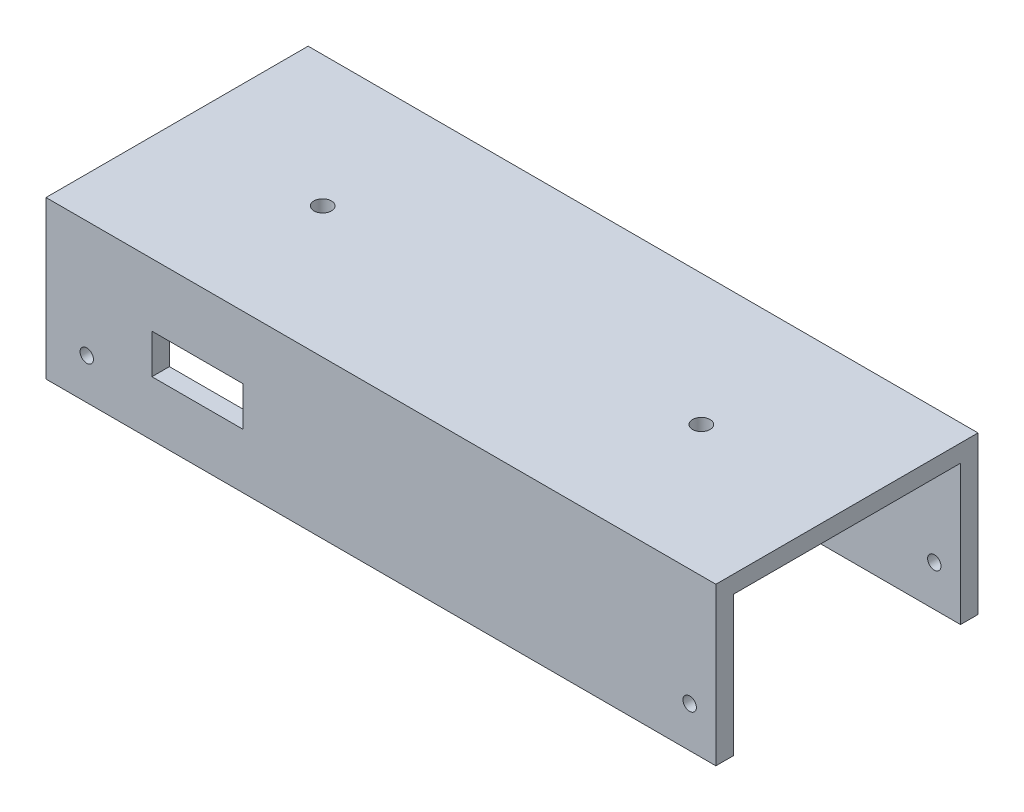
SolidWorks part; units mm, degrees
ref_plane "Front Plane" through (0, 0, 0) normal (0, 0, 1) x (1, 0, 0)
ref_plane "Top Plane" through (0, 0, 0) normal (0, 1, 0) x (1, 0, 0)
ref_plane "Right Plane" through (0, 0, 0) normal (1, 0, 0) x (0, 0, -1)
sketch "Sketch1" plane through (0, 0, 0) normal (0, 0, 1) x (1, 0, 0)
  line L9 (21.172, -17.9478) -> (91.172, -17.9478)
  line L10 (21.172, -17.9478) -> (21.172, -40.3878)
  line L11 (4.5, -8) -> (200.727, -8) construction
  line L12 (4.5, -8) -> (-67.0185, -8) construction
  line L13 (21.172, -40.3878) -> (91.172, -40.3878)
  line L14 (91.172, -17.9478) -> (91.172, -40.3878)
  line L15 (0, 0) -> (115, 0)
  line L16 (0, 0) -> (0, 27)
  line L17 (0, 27) -> (115, 27)
  line L18 (115, 0) -> (115, 27)
  circle A0 centre (4.5, 7) radius 1.15
  circle A1 centre (4.5, 7) radius 15 construction
  circle A3 centre (77.172, -29.1678) radius 3.6067
  circle A4 centre (110.5, 7) radius 15 construction
  circle A5 centre (110.5, 7) radius 1.15
  point P19 (21.172, -29.1678)
  dimension "D4" = 30
  dimension "D2" = 14
  dimension "D7" = 30
  dimension "D11" = 4.5
  dimension "D13" = 2.3
  dimension "D14" = 2.3
  dimension "D3" = 70
  dimension "D5" = 22.44
  dimension "D6" = 115
  dimension "D8" = 27
  dimension "D9" = 4.5
  dimension "D10" = 7
  dimension "D12" = 7
extrude "Boss-Extrude5" add sketch "Sketch1" along normal blind 45 contours L16 L15 L18 L17
shell "Shell9" thickness 3 removed face at (115, 13.5, 22.5) removed face at (57.5, 0, 22.5) removed face at (0, 13.5, 22.5)
sketch "Sketch3" plane through (0, 0, 0) normal (0, 0, -1) x (-1, 0, 0)
  line L0 (0, 0) -> (-115, 0) construction
  line L1 (-115, 0) -> (-115, 27) construction
  line L2 (0, 0) -> (0, 27) construction
  circle A0 centre (-7, 7) radius 1.15
  circle A1 centre (-110.5, 7) radius 1.15
  dimension "D1" = 2.3
  dimension "D2" = 2.3
  dimension "D3" = 7
  dimension "D4" = 4.5
  dimension "D5" = 7
  dimension "D6" = 7
extrude "Cut-Extrude2" cut sketch "Sketch3" against normal blind 79
sketch "Sketch6" plane through (0, 0, 0) normal (0, 0, -1) x (-1, 0, 0)
  line L0 (-71.9735, 19.9938) -> (-46.8835, 19.9938) construction
  line L1 (-71.9735, 21.7438) -> (-46.8835, 21.7438)
  line L2 (-71.9735, 18.2438) -> (-46.8835, 18.2438)
  line L7 (41.5249, -18.7743) -> (41.5249, -41.2143) construction
  line L8 (-89.8735, 11.4938) -> (-14.8735, 11.4938) construction
  line L9 (-89.8735, 15.9938) -> (-14.8735, 15.9938)
  line L10 (-89.8735, 6.9938) -> (-14.8735, 6.9938)
  line L11 (-14.8735, 11.4938) -> (-17.326, 11.4938) construction
  line L12 (-71.9735, 2.9938) -> (-46.8835, 2.9938) construction
  line L13 (-71.9735, 1.2438) -> (-46.8835, 1.2438)
  line L14 (-71.9735, 4.7438) -> (-46.8835, 4.7438)
  line L15 (4.7849, -29.9943) -> (74.7849, -29.9943) construction
  line L20 (4.7849, -18.7743) -> (74.7849, -18.7743)
  line L21 (4.7849, -18.7743) -> (4.7849, -41.2143)
  line L22 (4.7849, -41.2143) -> (74.7849, -41.2143)
  line L23 (74.7849, -18.7743) -> (74.7849, -41.2143)
  line L24 (-115, 0) -> (-115, 27) construction
  line L25 (63.3749, -18.7743) -> (63.3749, -41.2143) construction
  line L26 (0, 27) -> (-115, 27) construction
  arc A4 (-89.8735, 15.9938) -> (-89.8735, 6.9938) centre (-89.8735, 11.4938) ccw
  arc A5 (-71.9735, 21.7438) -> (-71.9735, 18.2438) centre (-71.9735, 19.9938) ccw
  arc A6 (-46.8835, 18.2438) -> (-46.8835, 21.7438) centre (-46.8835, 19.9938) ccw
  arc A7 (-14.8735, 6.9938) -> (-14.8735, 15.9938) centre (-14.8735, 11.4938) ccw
  arc A8 (-71.9735, 1.2438) -> (-71.9735, 4.7438) centre (-71.9735, 2.9938) cw
  arc A9 (-46.8835, 4.7438) -> (-46.8835, 1.2438) centre (-46.8835, 2.9938) cw
  circle A15 centre (16.1349, -29.9943) radius 1.5
  circle A16 centre (36.3249, -21.4943) radius 1.5
  circle A17 centre (36.3249, -38.4943) radius 1.5
  circle A18 centre (36.3249, -38.4943) radius 1.5
  circle A19 centre (27.0349, -29.9943) radius 2.3201
  point P11 (-59.4285, 19.9938)
  point P19 (-52.3735, 11.4938)
  point P31 (-59.4285, 2.9938)
  dimension "D8" = 1.75
  dimension "D13" = 4.5
  dimension "D10" = 3
  dimension "D14" = 3
  dimension "D9" = 25.09
  dimension "D2" = 8.5
  dimension "D3" = 17.9
  dimension "D4" = 70
  dimension "D5" = 22.44
  dimension "D6" = 36.74
  dimension "D7" = 11.35
  dimension "D11" = 5.2
  dimension "D12" = 8.5
  dimension "D15" = 22.25
  dimension "D16" = 75
  dimension "D17" = 25.1265
  dimension "D18" = 11.41
  dimension "D19" = 15.5062
extrude "Cut-Extrude8" cut sketch "Sketch6" against normal blind 23 contours L10 A7 L9 | L2 A6 L1 A5 | L13 A9 L14 A8 region at (59.4285, 19.9938, 0) region at (52.3735, 11.4938, 0)
sketch "Sketch7" plane through (0, 0, 45) normal (0, 0, 1) x (1, 0, 0)
  line L1 (18.1879, 16.2216) -> (33.7918, 16.2216)
  line L2 (18.1879, 16.2216) -> (18.1879, 9.4478)
  line L3 (18.1879, 9.4478) -> (33.7918, 9.4478)
  line L4 (33.7918, 16.2216) -> (33.7918, 9.4478)
extrude "Cut-Extrude9" cut sketch "Sketch7" against normal blind 20
sketch "Sketch9" plane through (0, 24, 0) normal (0, -1, 0) x (1, 0, 0)
  line L0 (0, 20.1086) -> (115, 20.1086) construction
  line L1 (0, 42) -> (0, 3) construction
  line L2 (115, 42) -> (115, 3) construction
  text T0 "group 3"
extrude "Cut-Extrude10" cut sketch "Sketch9" against normal blind 1
sketch "Sketch10" plane through (0, 24, 0) normal (0, -1, 0) x (1, 0, 0)
  line L0 (0, 42) -> (0, 3) construction
  line L1 (115, 42) -> (115, 3) construction
  circle A0 centre (25, 22.5) radius 1.5
  circle A1 centre (90, 22.5) radius 1.5
  point P8 (115, 22.5)
  dimension "D3" = 3
  dimension "D4" = 3
  dimension "D1" = 25
  dimension "D2" = 25
extrude "Cut-Extrude11" cut sketch "Sketch10" against normal blind 26
equation "\"slot­_width\"=25.09"
equation "\"D9@Sketch6\"=\"slot­_width\""
